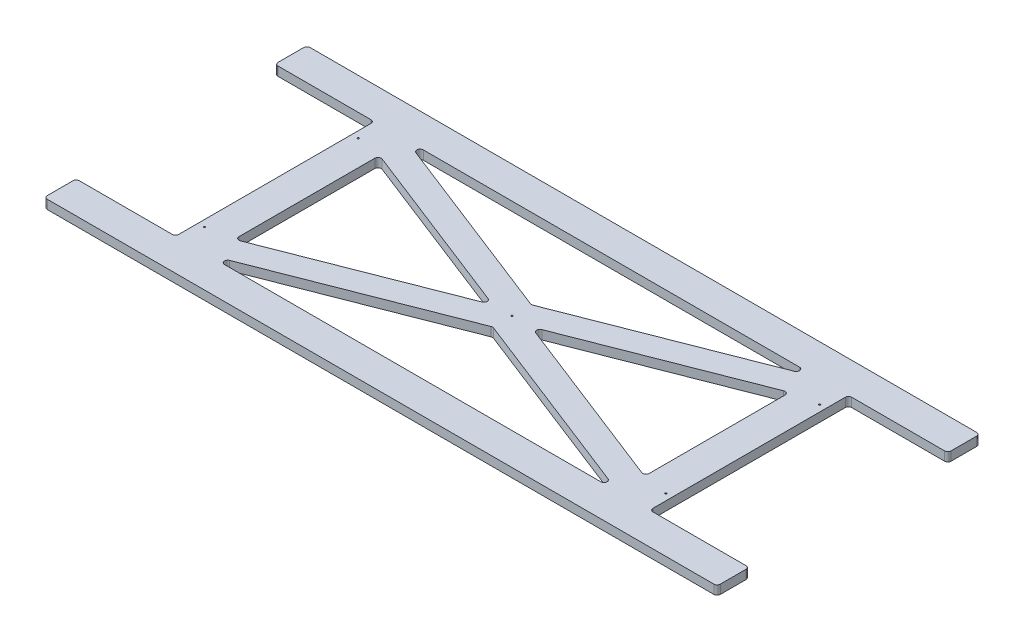
SolidWorks part; units mm, degrees
ref_plane "Front Plane" through (0, 0, 0) normal (0, 0, 1) x (1, 0, 0)
ref_plane "Top Plane" through (0, 0, 0) normal (0, 1, 0) x (1, 0, 0)
ref_plane "Right Plane" through (0, 0, 0) normal (1, 0, 0) x (0, 0, -1)
sketch "Sketch1" plane through (0, 0, 0) normal (0, 1, 0) x (1, 0, 0)
  line L1 (-666.75, 260.35) -> (666.75, 260.35)
  line L2 (-666.75, 260.35) -> (-666.75, -260.35)
  line L3 (-666.75, -260.35) -> (666.75, -260.35)
  line L4 (666.75, 260.35) -> (666.75, -260.35)
  line L5 (-666.75, 260.35) -> (666.75, -260.35) construction
  line L6 (-666.75, -260.35) -> (666.75, 260.35) construction
  point P0 (0, 0)
  dimension "D1" = 520.7
  dimension "D2" = 1333.5
extrude "Boss-Extrude1" add sketch "Sketch1" along normal blind 17.78
fillet "Fillet1" radius 6.35 4 edges at (-666.75, 8.89, 260.35) (-666.75, 8.89, -260.35) (666.75, 8.89, -260.35) (666.75, 8.89, 260.35)
hole_wizard "1/8 (0.125) Diameter Hole1" positions "Sketch3" profile "Sketch4" hole size "1/8" standard "ANSI Inch" end condition through all
sketch "Sketch3" plane through (0, 17.78, 0) normal (0, 1, 0) x (1, 0, 0)
  line L1 (-457.2, -152.4) -> (457.2, -152.4) construction
  line L2 (-457.2, -152.4) -> (-457.2, 152.4) construction
  line L3 (-457.2, 152.4) -> (457.2, 152.4) construction
  line L4 (457.2, -152.4) -> (457.2, 152.4) construction
  line L5 (-457.2, -152.4) -> (457.2, 152.4) construction
  line L6 (-457.2, 152.4) -> (457.2, -152.4) construction
  point P0 (0, 0)
  point P1 (457.2, 152.4)
  point P32 (-457.2, -152.4)
  point P33 (-457.2, 152.4)
  point P34 (457.2, -152.4)
  dimension "D1" = 914.4
  dimension "D2" = 304.8
sketch "Sketch4" plane through (0, 17.78, 0) normal (1, 0, 0) x (0, 0, 1)
  line L0 (0, 0) -> (0, 17.78)
  line L1 (0, 17.78) -> (1.5875, 17.78)
  line L2 (1.5875, 17.78) -> (1.5875, 0)
  line L5 (1.5875, 0) -> (0, 0)
  line L11 (0, -6.35) -> (0, 107.95) construction
  dimension "Thru Hole Dia." = 3.175
  dimension "Thru Hole Depth" = 17.78
sketch "Sketch2" plane through (0, 17.78, 0) normal (0, 1, 0) x (1, 0, 0)
  line L1 (-635, -330.2) -> (635, -330.2)
  line L2 (-635, -330.2) -> (-635, 330.2)
  line L3 (-635, 330.2) -> (635, 330.2)
  line L4 (635, -330.2) -> (635, 330.2)
  line L5 (-635, -330.2) -> (635, 330.2) construction
  line L6 (-635, 330.2) -> (635, -330.2) construction
  point P0 (0, 0)
  dimension "D1" = 660.4
  dimension "D2" = 1270
extrude "Boss-Extrude2" [suppressed] add sketch "Sketch2" along normal blind 9.525
sketch "Sketch5" plane through (0, 17.78, 0) normal (0, 1, 0) x (1, 0, 0)
  line L0 (-406.4, 196.85) -> (406.4, 196.85)
  line L1 (660.4, 260.35) -> (-660.4, 260.35) construction
  line L2 (0, 38.1) -> (-406.4, 196.85)
  line L3 (406.4, 196.85) -> (0, 38.1)
  line L4 (0, 260.35) -> (0, -260.35) construction
  line L5 (-660.4, -260.35) -> (660.4, -260.35) construction
  line L6 (-666.75, 0) -> (666.75, 0) construction
  line L7 (-666.75, 254) -> (-666.75, -254) construction
  line L8 (666.75, -254) -> (666.75, 254) construction
  line L9 (0, -38.1) -> (-406.4, -196.85)
  line L10 (-406.4, -196.85) -> (406.4, -196.85)
  line L11 (406.4, -196.85) -> (0, -38.1)
  line L12 (406.4, 143.8672) -> (406.4, -143.8672)
  line L13 (406.4, -143.8672) -> (38.1, 0)
  line L14 (406.4, 143.8672) -> (38.1, 0)
  line L15 (-406.4, 143.8672) -> (-38.1, 0)
  line L16 (-406.4, 143.8672) -> (-406.4, -143.8672)
  line L17 (-406.4, -143.8672) -> (-38.1, 0)
  line L18 (622.3, -196.85) -> (469.9, -196.85)
  line L19 (-622.3, -196.85) -> (-469.9, -196.85)
  line L20 (-622.3, -196.85) -> (-622.3, 196.85)
  line L21 (-622.3, 196.85) -> (-469.9, 196.85)
  line L22 (-469.9, -196.85) -> (-469.9, 196.85)
  line L23 (-622.3, -196.85) -> (-469.9, 196.85) construction
  line L24 (-622.3, 196.85) -> (-469.9, -196.85) construction
  line L25 (622.3, -196.85) -> (622.3, 196.85)
  line L26 (622.3, 196.85) -> (469.9, 196.85)
  line L27 (469.9, -196.85) -> (469.9, 196.85)
  circle A0 centre (0, 0) radius 38.1 construction
  point P3 (0, 196.85)
  point P30 (-546.1, 0)
  dimension "D2" = 76.2
  dimension "D4" = 152.4
  dimension "D1" = 63.5
  dimension "D3" = 812.8
  dimension "D5" = 44.45
extrude "Cut-Extrude1" cut sketch "Sketch5" against normal through all
fillet "Fillet2" radius 6.35 20 edges at (469.9, 8.89, -196.85) (469.9, 8.89, 196.85) (622.3, 8.89, 196.85) (406.4, 8.89, 143.8672) (406.4, 8.89, 196.85) (622.3, 8.89, -196.85) (406.4, 8.89, -143.8672) (406.4, 8.89, -196.85) (38.1, 8.89, 0) (0, 8.89, 38.1) (0, 8.89, -38.1) (-38.1, 8.89, 0) (-406.4, 8.89, 196.85) (-406.4, 8.89, -196.85) (-406.4, 8.89, -143.8672) (-406.4, 8.89, 143.8672) (-622.3, 8.89, 196.85) (-469.9, 8.89, 196.85) (-469.9, 8.89, -196.85) (-622.3, 8.89, -196.85)
sketch "Sketch6" plane through (0, 17.78, 0) normal (0, 1, 0) x (1, 0, 0)
  line L0 (666.75, -254) -> (666.75, 254) construction
  line L1 (615.95, -196.85) -> (666.75, -196.85)
  line L2 (615.95, -196.85) -> (615.95, 196.85)
  line L3 (615.95, 196.85) -> (666.75, 196.85)
  line L4 (666.75, -196.85) -> (666.75, 196.85)
  line L5 (-666.75, 254) -> (-666.75, -254) construction
  line L6 (-615.95, -196.85) -> (-666.75, -196.85)
  line L7 (-615.95, -196.85) -> (-615.95, 196.85)
  line L8 (-615.95, 196.85) -> (-666.75, 196.85)
  line L9 (-666.75, -196.85) -> (-666.75, 196.85)
extrude "Cut-Extrude2" cut sketch "Sketch6" against normal through all
fillet "Fillet3" radius 6.35 4 edges at (-666.75, 8.89, 196.85) (-666.75, 8.89, -196.85) (666.75, 8.89, -196.85) (666.75, 8.89, 196.85)
